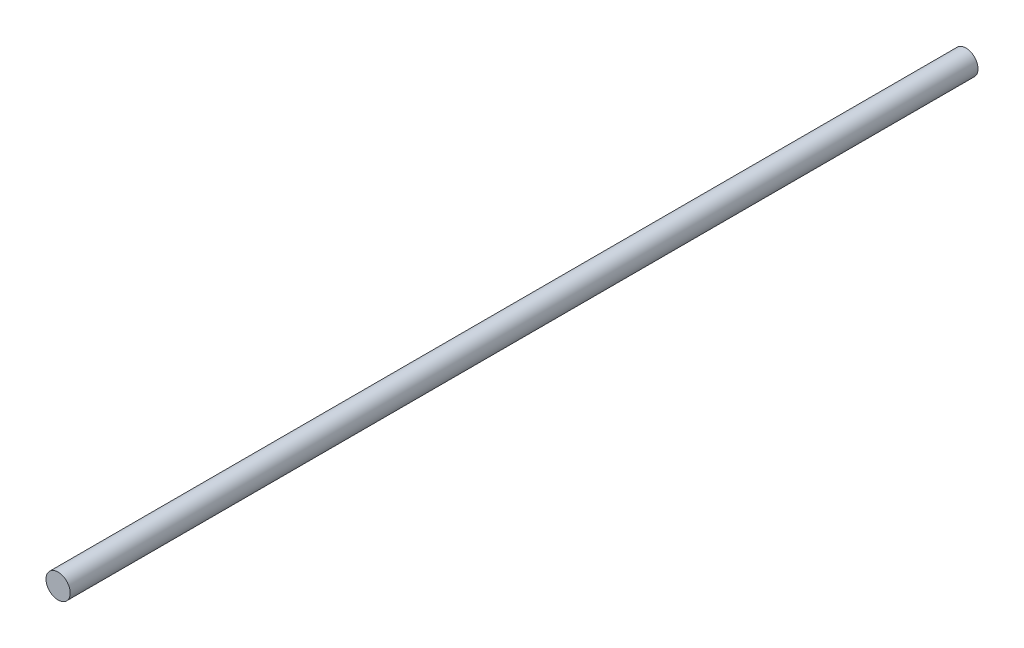
SolidWorks part; units mm, degrees
ref_plane "Спереди" through (0, 0, 0) normal (0, 0, 1) x (1, 0, 0)
ref_plane "Сверху" through (0, 0, 0) normal (0, 1, 0) x (1, 0, 0)
ref_plane "Справа" through (0, 0, 0) normal (1, 0, 0) x (0, 0, -1)
sketch "Эскиз1" plane through (0, 0, 0) normal (0, 0, 1) x (1, 0, 0)
  circle A0 centre (0, 0) radius 6
  dimension "D1" = 12
extrude "Бобышка-Вытянуть1" add sketch "Эскиз1" along normal blind 450
